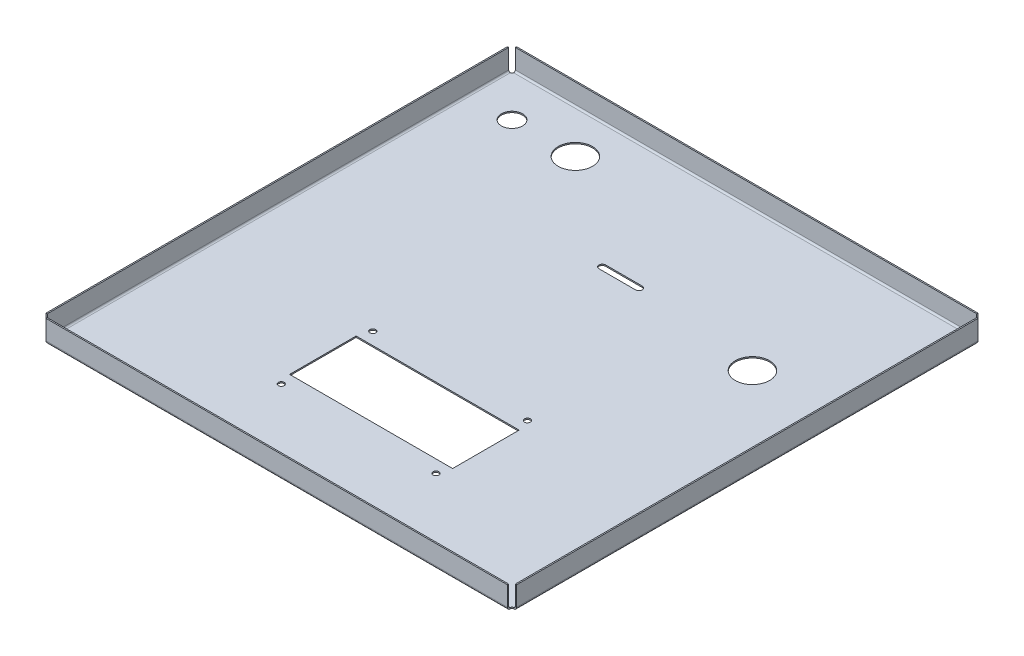
SolidWorks part; units mm, degrees
note: The reader was unsure of these and kept them because the rebuilt part matched: flange length of "Edge-Flange1".
ref_plane "Front Plane" through (0, 0, 0) normal (0, 0, 1) x (1, 0, 0)
ref_plane "Top Plane" through (0, 0, 0) normal (0, 1, 0) x (1, 0, 0)
ref_plane "Right Plane" through (0, 0, 0) normal (1, 0, 0) x (0, 0, -1)
sketch "Sketch1" plane through (0, 0, 0) normal (0, 1, 0) x (1, 0, 0)
  line L1 (0, 0) -> (279.4, 0)
  line L2 (0, 0) -> (0, 279.4)
  line L3 (0, 279.4) -> (279.4, 279.4)
  line L4 (279.4, 0) -> (279.4, 279.4)
  dimension "D1" = 279.4
  dimension "D2" = 279.4
sheet metal parameters "Sheet-Metal1" thickness 0.7595 parameters "D1"=6.35
base flange "Base-Flange1" sketch "Sketch1" thickness 0.7595 reverse thickness direction yes parameters "D1"=6.35
sketch "Sketch4" plane through (0, 0.7595, 0) normal (0, 1, 0) x (1, 0, 0)
  line L0 (279.4, 0) -> (279.4, 279.4) construction
  circle A0 centre (0, 0) radius 1
  circle A1 centre (0, 279.4) radius 1
  circle A2 centre (279.4, 279.4) radius 1
  circle A3 centre (279.4, 0) radius 1
  dimension "D1" = 2
extrude "Cut-Extrude1" cut sketch "Sketch4" against normal through all normal cut yes
edge flange "Edge-Flange1" sketch "Sketch13" flange profiles "Sketch13", "Sketch14", "Sketch15", "Sketch16" flange angle 90 flange length 12.7 flange position bend outside bend radius 1 thickness 0.7595 relief rectangular gap distance 1 parameters "D6"=10, "D8"=1
sketch "Sketch13" plane through (0, 0.7595, -279.4) normal (0, 0, -1) x (-1, 0, 0)
  line L2 (-278.4, 0) -> (-278.4, 12.7)
  line L3 (-278.4, 12.7) -> (-1, 12.7)
  line L4 (-1, 12.7) -> (-1, 0)
  line L5 (-278.4, 0) -> (-1, 0) construction
  line L6 (-278.4, 0) -> (-1, 0)
sketch "Sketch14" plane through (0, 0.7595, 0) normal (-1, 0, 0) x (0, 0, 1)
  line L0 (-278.4, 0) -> (-1, 0) construction
  line L1 (-278.4, 0) -> (-1, 0)
  line L2 (-278.4, 0) -> (-278.4, 12.7)
  line L3 (-278.4, 12.7) -> (-1, 12.7)
  line L4 (-1, 12.7) -> (-1, 0)
sketch "Sketch15" plane through (0, 0.7595, 0) normal (0, 0, 1) x (1, 0, 0)
  line L0 (1, 0) -> (278.4, 0) construction
  line L1 (1, 0) -> (278.4, 0)
  line L2 (1, 0) -> (1, 12.7)
  line L3 (1, 12.7) -> (278.4, 12.7)
  line L4 (278.4, 12.7) -> (278.4, 0)
sketch "Sketch16" plane through (279.4, 0.7595, 0) normal (1, 0, 0) x (0, 0, -1)
  line L0 (1, 0) -> (278.4, 0) construction
  line L1 (1, 0) -> (278.4, 0)
  line L2 (1, 0) -> (1, 12.7)
  line L3 (1, 12.7) -> (278.4, 12.7)
  line L4 (278.4, 12.7) -> (278.4, 0)
bend "EdgeBend1" bend radius 1 bend angle 90 parameters "D5"=1
bend "EdgeBend2" bend radius 1 bend angle 90 parameters "D5"=2
bend "EdgeBend3" bend radius 1 bend angle 90 parameters "D5"=3
bend "EdgeBend4" bend radius 1 bend angle 90 parameters "D5"=4
sketch "Sketch17" plane through (0, 0, 0) normal (0, -1, 0) x (1, 0, 0)
  line L0 (1, 0) -> (278.4, 0) construction
  line L1 (90.7, -55) -> (188.7, -55)
  line L2 (90.7, -55) -> (90.7, -95)
  line L3 (90.7, -95) -> (188.7, -95)
  line L4 (188.7, -55) -> (188.7, -95)
  line L5 (139.7, 0) -> (139.7, -55) construction
  line L6 (139.7, -95) -> (139.7, -135) construction
  line L7 (105.2, -135) -> (174.2, -135) construction
  line L8 (105.2, -135) -> (105.2, -211) construction
  line L9 (105.2, -211) -> (174.2, -211) construction
  line L10 (174.2, -135) -> (174.2, -211) construction
  line L12 (0, -278.4) -> (0, -1) construction
  line L13 (278.4, -279.4) -> (1, -279.4) construction
  line L14 (279.4, -1) -> (279.4, -278.4) construction
  line L15 (128.7, -205) -> (150.7, -205) construction
  line L17 (128.7, -203) -> (150.7, -203)
  line L18 (128.7, -207) -> (150.7, -207)
  circle A0 centre (25, -254.4) radius 6.35
  circle A1 centre (63.1, -254.4) radius 10.3188
  circle A2 centre (227.84, -196.11) radius 10.3187
  arc A3 (128.7, -203) -> (128.7, -207) centre (128.7, -205) ccw
  arc A4 (150.7, -207) -> (150.7, -203) centre (150.7, -205) ccw
  point P28 (139.7, -205)
  point P33 (139.7, -211)
  dimension "D7" = 12.7
  dimension "D8" = 20.6375
  dimension "D12" = 20.6375
  dimension "D15" = 2
  dimension "D1" = 55
  dimension "D2" = 40
  dimension "D3" = 98
  dimension "D4" = 69
  dimension "D5" = 76
  dimension "D6" = 40
  dimension "D9" = 38.1
  dimension "D10" = 25
  dimension "D11" = 25
  dimension "D13" = 83.29
  dimension "D14" = 51.56
  dimension "D16" = 22
  dimension "D17" = 4
extrude "Cut-Extrude2" cut sketch "Sketch17" against normal up to next normal cut yes
sketch "Sketch19" plane through (0, 0, 0) normal (0, -1, 0) x (1, 0, 0)
  line L1 (93.2, -47.5) -> (186.2, -47.5) construction
  line L2 (93.2, -47.5) -> (93.2, -102.5) construction
  line L3 (93.2, -102.5) -> (186.2, -102.5) construction
  line L4 (186.2, -47.5) -> (186.2, -102.5) construction
  line L5 (139.7, -47.5) -> (139.7, -55) construction
  line L6 (188.7, -55) -> (90.7, -55) construction
  line L7 (93.2, -75) -> (90.7, -75) construction
  line L8 (90.7, -55) -> (90.7, -95) construction
  circle A0 centre (93.2, -47.5) radius 1.75
  circle A1 centre (186.2, -47.5) radius 1.75
  circle A2 centre (186.2, -102.5) radius 1.75
  circle A3 centre (93.2, -102.5) radius 1.75
  dimension "D3" = 3.5
  dimension "D1" = 55
  dimension "D2" = 93
extrude "Cut-Extrude4" cut sketch "Sketch19" against normal through all normal cut yes
flat pattern "Flat-Pattern1" [suppressed]
sketch "Bend-Lines1" plane through (0, 0, 0) normal (0, -1, 0) x (-1, 0, 0)
  line L0 (-280.4836, 278.4) -> (-280.4836, 1) construction
  line L1 (-278.4, -1.0836) -> (-1, -1.0836) construction
  line L2 (1.0836, 1) -> (1.0836, 278.4) construction
  line L3 (-1, 280.4836) -> (-278.4, 280.4836) construction
  line L4 (-280.4836, 278.4) -> (-280.4836, 1) construction
  line L5 (-278.4, -1.0836) -> (-1, -1.0836) construction
  line L6 (1.0836, 1) -> (1.0836, 278.4) construction
  line L7 (-1, 280.4836) -> (-278.4, 280.4836) construction
sketch3d "Bounding-Box1" [suppressed]
  line L0 (13.8673, -13.8673, 0) -> (13.8673, 293.2673, 0) construction
  line L1 (-293.2673, -13.8673, 0) -> (-293.2673, 293.2673, 0) construction
  line L2 (13.8673, -13.8673, 0) -> (-293.2673, -13.8673, 0) construction
  line L3 (13.8673, 293.2673, 0) -> (-293.2673, 293.2673, 0) construction
bend of the flat pattern "Flatten-<EdgeBend1>1"
bend of the flat pattern "Flatten-<EdgeBend2>1"
bend of the flat pattern "Flatten-<EdgeBend3>1"
bend of the flat pattern "Flatten-<EdgeBend4>1"
sketch "Sketch20" [suppressed] plane through (0, 0, 0) normal (0, -1, 0) x (1, 0, 0)
  line L0 (139.7, -95) -> (139.7, -125) construction
  line L1 (105.2, -125) -> (174.2, -125)
  line L2 (105.2, -125) -> (105.2, -201)
  line L3 (105.2, -201) -> (174.2, -201)
  line L4 (174.2, -125) -> (174.2, -201)
  line L5 (90.7, -95) -> (188.7, -95) construction
  line L6 (139.7, -125) -> (139.7, -194) construction
  line L7 (125.7, -194) -> (153.7, -194)
  line L8 (125.7, -194) -> (125.7, -198)
  line L9 (125.7, -198) -> (153.7, -198)
  line L10 (153.7, -194) -> (153.7, -198)
  dimension "D1" = 76
  dimension "D2" = 69
  dimension "D3" = 30
  dimension "D4" = 4
  dimension "D5" = 28
  dimension "D6" = 69
